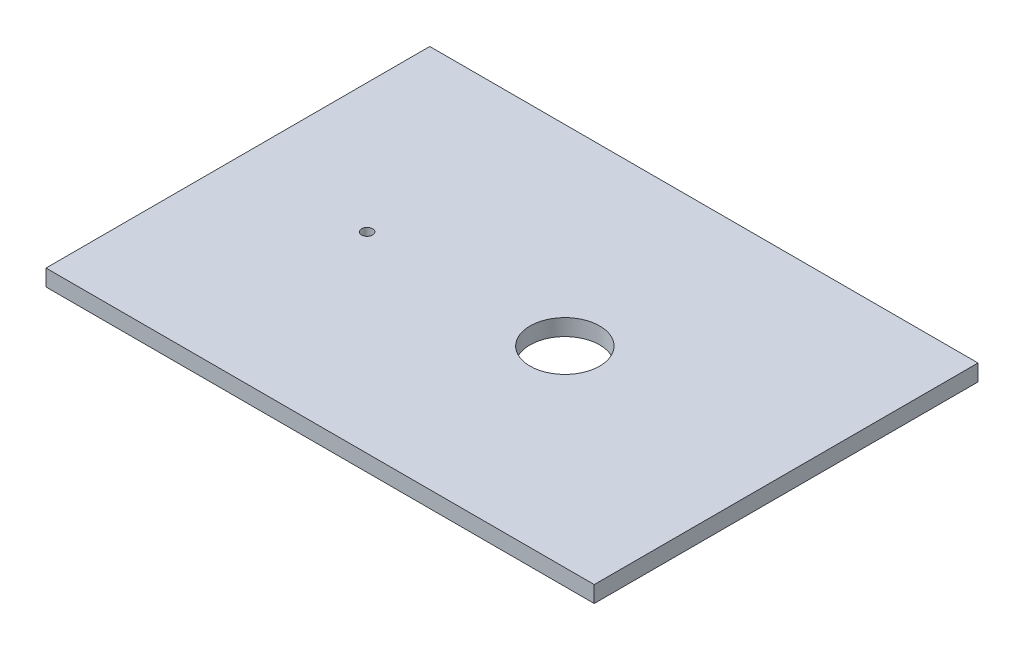
SolidWorks part; units mm, degrees
ref_plane "Front Plane" through (0, 0, 0) normal (0, 0, 1) x (1, 0, 0)
ref_plane "Top Plane" through (0, 0, 0) normal (0, 1, 0) x (1, 0, 0)
ref_plane "Right Plane" through (0, 0, 0) normal (1, 0, 0) x (0, 0, -1)
sketch "Sketch2" plane through (0, 0, 0) normal (0, 1, 0) x (1, 0, 0)
  line L1 (-50, -35) -> (50, -35)
  line L2 (-50, -35) -> (-50, 35)
  line L3 (-50, 35) -> (50, 35)
  line L4 (50, -35) -> (50, 35)
  line L5 (-50, -35) -> (50, 35) construction
  line L6 (-50, 35) -> (50, -35) construction
  point P0 (0, 0)
  dimension "D1" = 100
  dimension "D2" = 70
base flange "Base-Flange1" sketch "Sketch2" thickness 3 reverse thickness direction no parameters "D1"=1
sketch "Sketch7" plane through (0, 0, 0) normal (0, 1, 0) x (1, 0, 0)
  line L0 (-50, 0) -> (-26.43, 0)
  line L1 (-50, -35) -> (-50, 35) construction
  line L2 (-26.43, 0) -> (9.64, 0)
  circle A0 centre (-26.43, 0) radius 1
  circle A1 centre (9.64, 0) radius 6.35
  dimension "D2" = 36.07
  dimension "D1" = 23.57
extrude "Cut-Extrude1" cut sketch "Sketch7" against normal blind 10
sketch "Bend-Lines1" [suppressed] plane through (0, 0, 0) normal (0, 1, 0) x (1, 0, 0)
sketch "Bounding-Box1" [suppressed] plane through (0, 0, 0) normal (0, 1, 0) x (1, 0, 0)
sheet metal parameters "Sheet-Metal1" thickness 3 parameters "D1"=1
flat pattern "Flat-Pattern1" [suppressed]
sketch "Bend-Lines2" plane through (0, 0, 0) normal (0, 1, 0) x (1, 0, 0)
sketch3d "Bounding-Box2" [suppressed]
  line L0 (-50, 35, 0) -> (50, 35, 0) construction
  line L1 (-50, -35, 0) -> (50, -35, 0) construction
  line L2 (-50, 35, 0) -> (-50, -35, 0) construction
  line L3 (50, 35, 0) -> (50, -35, 0) construction
sheet metal parameters "Sheet-Metal2" thickness 3 parameters "D1"=1
flat pattern "Flat-Pattern1"
sketch "Bend-Lines2" plane through (0, 0, 0) normal (0, 1, 0) x (1, 0, 0)
sketch3d "Bounding-Box2" [suppressed]
  line L0 (50, 35, 0) -> (-50, 35, 0) construction
  line L1 (50, -35, 0) -> (-50, -35, 0) construction
  line L2 (50, 35, 0) -> (50, -35, 0) construction
  line L3 (-50, 35, 0) -> (-50, -35, 0) construction
